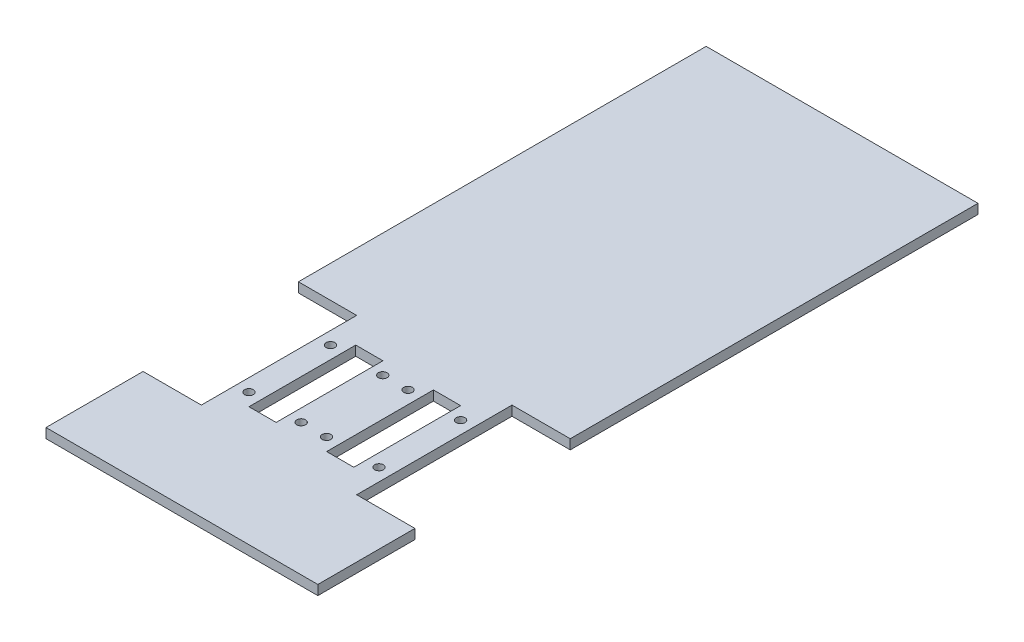
SolidWorks part; units mm, degrees
ref_plane "Front Plane" through (0, 0, 0) normal (0, 0, 1) x (1, 0, 0)
ref_plane "Top Plane" through (0, 0, 0) normal (0, 1, 0) x (1, 0, 0)
ref_plane "Right Plane" through (0, 0, 0) normal (1, 0, 0) x (0, 0, -1)
sketch "Sketch1" plane through (0, 0, 0) normal (0, 1, 0) x (1, 0, 0)
  line L1 (-70, -170) -> (70, -170)
  line L2 (-70, -170) -> (-70, 170)
  line L3 (-70, 170) -> (70, 170)
  line L4 (70, -170) -> (70, 170)
  line L5 (-70, -170) -> (70, 170) construction
  line L6 (-70, 170) -> (70, -170) construction
  point P0 (0, 0)
  dimension "D1" = 140
  dimension "D2" = 340
extrude "Boss-Extrude1" add sketch "Sketch1" along normal blind 5
sketch "Sketch3" plane through (0, 5, 0) normal (0, 1, 0) x (1, 0, 0)
  line L0 (0, 170) -> (0, -170) construction
  line L1 (70, 170) -> (-70, 170) construction
  line L2 (-70, -170) -> (70, -170) construction
  line L3 (-70, -120) -> (70, -120)
  line L4 (-70, 170) -> (-70, -170) construction
  line L5 (70, -170) -> (70, 170) construction
  line L6 (-70, -40) -> (70, -40)
  line L7 (-40, -40) -> (-40, -120)
  line L8 (40, -40) -> (40, -120)
  line L9 (-70, -40) -> (-70, -121.1832)
  line L10 (70, -40) -> (70, -120)
  line M1 (70, -170) -> (70, 170)
  line M3 (-70, 170) -> (-70, -170)
  dimension "D1" = 50
  dimension "D2" = 80
  dimension "D3" = 30
  dimension "D4" = 30
extrude "Cut-Extrude1" cut sketch "Sketch3" against normal through all contours L7 L6 L3 M3 | L6 L8 L3 M1 region at (-55, 5, 80) region at (55, 5, 80)
sketch "Sketch5" plane through (0, 0, 0) normal (0, -1, 0) x (-1, 0, 0)
  line L0 (-40, -108.473) -> (40.1724, -108.473)
  line L1 (-40, -40) -> (-40, -120) construction
sketch "Sketch6" plane through (0, 0, 0) normal (0, -1, 0) x (-1, 0, 0)
  line L0 (-40, -40) -> (-40, -120) construction
  line L1 (0.0862, -108.473) -> (0.0862, -54.3323) construction
  line L2 (-40, -108.473) -> (40.1724, -108.473) construction
  line L3 (-12.9462, -108.473) -> (13.1186, -108.473)
  line L4 (-12.9462, -108.473) -> (-12.9462, -101.973)
  line L5 (13.1186, -108.473) -> (13.1186, -101.973)
  circle A0 centre (-33.5, -101.973) radius 2.25
  circle A1 centre (-33.5, -59.973) radius 2.25
  circle A2 centre (33.5, -101.973) radius 2.25
  circle A3 centre (33.5, -59.973) radius 2.25
  circle A4 centre (6.6186, -101.973) radius 2.25
  circle A5 centre (-6.4462, -101.973) radius 2.25
  circle A6 centre (6.6186, -59.973) radius 2.25
  circle A7 centre (-6.4462, -59.973) radius 2.25
  point P20 (0.0862, -108.473)
  dimension "D1" = 6.5
extrude "Cut-Extrude2" cut sketch "Sketch6" against normal through all contours A1 | A0 | A7 | A5 | A4 | A6 | A3 | A2 region at (33.5, 0, 101.973) region at (33.5, 0, 59.973) region at (-33.5, 0, 101.973) region at (-33.5, 0, 59.973) region at (-6.6186, 0, 101.973) region at (6.4462, 0, 101.973) region at (-6.6186, 0, 59.973) region at (6.4462, 0, 59.973)
sketch "Sketch7" plane through (0, 0, 0) normal (0, -1, 0) x (-1, 0, 0)
  line L0 (-40, -108.473) -> (40.1724, -108.473) construction
  line L1 (-12.9462, -108.473) -> (-27, -108.473)
  line L2 (-12.9462, -108.473) -> (-12.9462, -53.473)
  line L3 (-12.9462, -53.473) -> (-27, -53.473)
  line L4 (-27, -108.473) -> (-27, -53.473)
  line L5 (-12.9462, -94.973) -> (-12.9462, -108.473) construction
  line L6 (27, -108.473) -> (27, -89.973) construction
  line L7 (27, -108.473) -> (13.1186, -108.473)
  line L8 (27, -108.473) -> (27, -53.473)
  line L9 (27, -53.473) -> (13.1186, -53.473)
  line L10 (13.1186, -108.473) -> (13.1186, -53.473)
  dimension "D1" = 55
sketch "Sketch8" plane through (0, 0, 0) normal (0, -1, 0) x (1, 0, 0)
  line L0 (12.9462, 53.473) -> (27, 53.473) construction
  line L1 (27, 108.473) -> (27, 53.473) construction
  line L2 (12.9462, 108.473) -> (12.9462, 53.473) construction
  line L3 (-27, 53.473) -> (-13.1186, 53.473) construction
  line L4 (-13.1186, 108.473) -> (-13.1186, 53.473) construction
  line L5 (-27, 108.473) -> (-27, 53.473) construction
  line L6 (12.9462, 53.473) -> (27, 53.473)
  line L7 (27, 108.473) -> (27, 53.473)
  line L8 (12.9462, 108.473) -> (12.9462, 53.473)
  line L9 (-27, 53.473) -> (-13.1186, 53.473)
  line L10 (-13.1186, 108.473) -> (-13.1186, 53.473)
  line L11 (-27, 108.473) -> (-27, 53.473)
  line L12 (-27, 108.473) -> (-13.1186, 108.473)
  line L13 (12.9462, 108.473) -> (27, 108.473)
sketch "Sketch9" plane through (0, 0, 0) normal (0, -1, 0) x (1, 0, 0)
  line L0 (-27, 108.473) -> (-27, 53.473)
  line L1 (40, 108.473) -> (-40.1724, 108.473) construction
  line L2 (-27, 53.473) -> (-13, 53.473)
  line L3 (-13, 53.473) -> (-13, 108.473)
  line L4 (-13, 108.473) -> (-27, 108.473)
  line L5 (13, 108.473) -> (13, 53.473)
  line L6 (13, 53.473) -> (27, 53.473)
  line L7 (27, 53.473) -> (27, 108.473)
  line L8 (27, 108.473) -> (13, 108.473)
  line L9 (-40, 40) -> (-40, 120) construction
  line L10 (40, 40) -> (40, 120) construction
  dimension "D1" = 14
  dimension "D2" = 13
  dimension "D3" = 13
  dimension "D4" = 14
  dimension "D5" = 55
  dimension "D6" = 55
extrude "Cut-Extrude3" cut sketch "Sketch9" against normal through all
